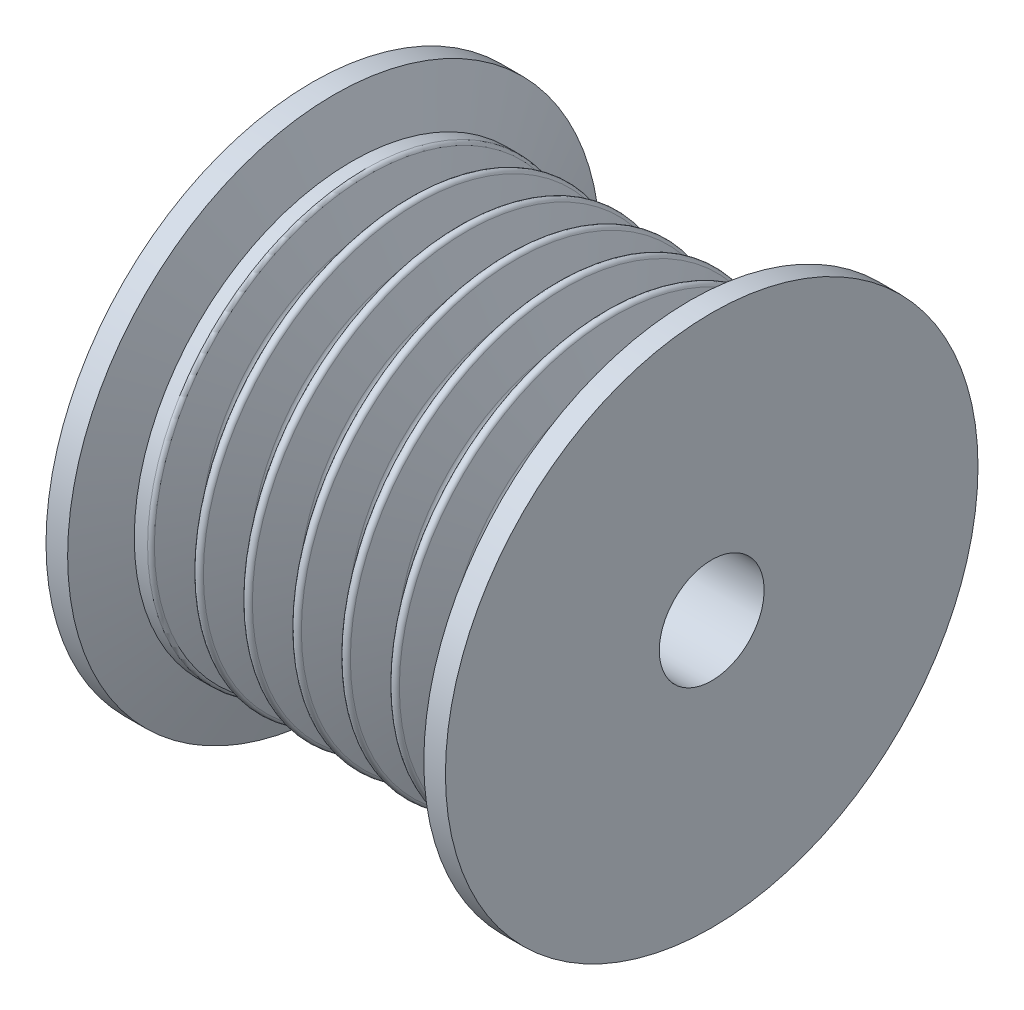
SolidWorks part; units mm, degrees
ref_plane "Front Plane" through (0, 0, 0) normal (0, 0, 1) x (1, 0, 0)
ref_plane "Top Plane" through (0, 0, 0) normal (0, 1, 0) x (1, 0, 0)
ref_plane "Right Plane" through (0, 0, 0) normal (1, 0, 0) x (0, 0, -1)
sketch "Sketch1" plane through (0, 0, 0) normal (0, 0, 1) x (1, 0, 0)
  line L0 (0, 0) -> (0, 2.5) construction
  line L1 (0, 2.5) -> (19.05, 2.5)
  line L2 (19.05, 2.5) -> (19.05, 12.7)
  line L3 (19.05, 12.7) -> (0, 12.7)
  line L4 (0, 12.7) -> (0, 2.5)
  line L5 (0, 0) -> (13.5959, 0) construction
  dimension "D1" = 25.4
  dimension "D2" = 5
  dimension "D3" = 19.05
revolve "Revolve1" add sketch "Sketch1" angle 360 about L5
sketch "Sketch2" plane through (0, 0, 0) normal (0, 0, 1) x (1, 0, 0)
  line L0 (14.1986, 12.7) -> (14.1986, 10.3699)
  line L2 (14.3895, 10.2362) -> (14.9851, 8.5999)
  line L3 (15.7489, 8.5999) -> (16.3445, 10.2362)
  line L4 (16.5354, 10.3699) -> (16.5354, 12.7)
  line L5 (16.5354, 12.7) -> (14.1986, 12.7)
  line L6 (14.1986, 11.43) -> (16.5354, 11.43) construction
  line L7 (0, 0) -> (24.4755, 0) construction
  line L8 (14.3895, 10.2362) -> (16.3445, 10.2362) construction
  line L9 (14.1986, 12.7) -> (11.8618, 12.7) construction
  line L10 (19.05, 12.7) -> (0, 12.7) construction
  line L11 (11.8618, 12.7) -> (9.525, 12.7) construction
  arc A0 (14.1986, 10.3699) -> (14.3895, 10.2362) centre (14.1986, 10.1667) cw
  arc A1 (14.9851, 8.5999) -> (15.7489, 8.5999) centre (15.367, 8.7389) ccw
  arc A2 (16.3445, 10.2362) -> (16.5354, 10.3699) centre (16.5354, 10.1667) cw
  point P2 (9.525, 12.7)
  dimension "D1" = 0.4064
  dimension "D5" = 0.2032
  dimension "D2" = 2.3368
  dimension "D3" = 11.43
  dimension "D4" = 1.1938
  dimension "D6" = 40
revolve "Cut-Revolve1" cut sketch "Sketch2" angle 360 about L7
pattern_linear "LPattern1" count 6 spacing 2.3368 along (-1, 0, 0) of "Cut-Revolve1"
sketch "Sketch3" plane through (0, 0, 0) normal (0, 0, 1) x (1, 0, 0)
  line L0 (16.5354, 12.7) -> (18.0185, 12.7)
  line L1 (19.05, 12.7) -> (16.5354, 12.7) construction
  line L2 (18.0185, 12.7) -> (17.1704, 10.3699)
  line L3 (17.1704, 10.3699) -> (16.5354, 10.3699)
  line L4 (16.5354, 12.7) -> (16.5354, -12.7) construction
  line L5 (16.5354, 10.3699) -> (16.5354, 12.7)
  line L6 (16.5354, 10.3699) -> (16.5354, -10.3699) construction
  line L7 (15.367, 8.3325) -> (15.367, 11.4458) construction
  line L8 (9.525, 10.3699) -> (9.525, 14.7012) construction
  line L9 (2.5146, 10.3699) -> (2.5146, 12.7)
  line L10 (1.8796, 10.3699) -> (2.5146, 10.3699)
  line L11 (1.0315, 12.7) -> (1.8796, 10.3699)
  line L12 (2.5146, 12.7) -> (1.0315, 12.7)
  line L13 (0, 0) -> (26.9583, 0) construction
  arc A0 (14.9851, 8.5999) -> (15.7489, 8.5999) centre (15.367, 8.7389) ccw construction
  arc A1 (9.7159, 10.2362) -> (9.3341, 10.2362) centre (9.525, 10.1667) ccw construction
  dimension "D1" = 1.8034
  dimension "D2" = 20
revolve "Cut-Revolve2" cut sketch "Sketch3" angle 360 about L13
equation "\"D2@Sketch1\"=5mm"
equation "\"D3@Sketch2\"=0.9in/2"
equation "\"D4@Sketch2\"=0.094in/2"
